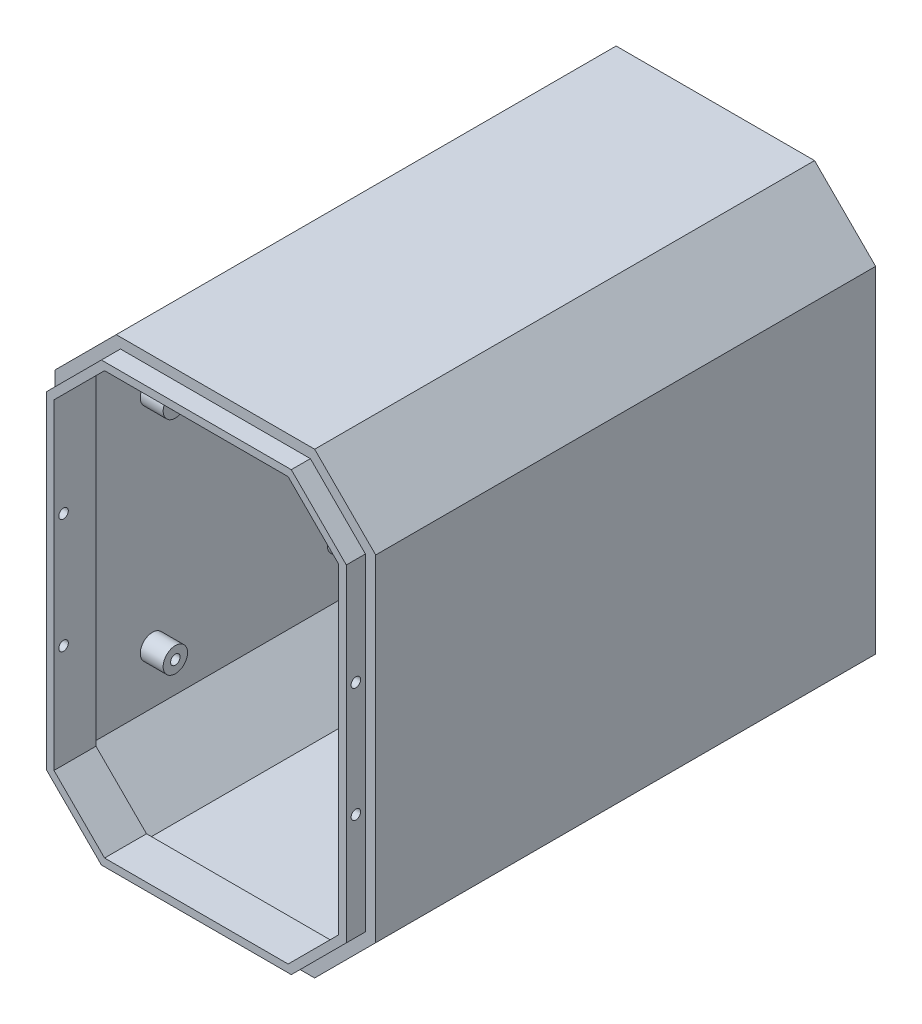
SolidWorks part; units mm, degrees
ref_plane "Front Plane" through (0, 0, 0) normal (0, 0, 1) x (1, 0, 0)
ref_plane "Top Plane" through (0, 0, 0) normal (0, 1, 0) x (1, 0, 0)
ref_plane "Right Plane" through (0, 0, 0) normal (1, 0, 0) x (0, 0, -1)
ref_plane "PZ_p37_000" through (0, 0, 37) normal (0, 0, 1) x (1, 0, 0)
sketch "S_prism1" plane through (0, 0, 37) normal (0, 0, 1) x (1, 0, 0)
  line L0 (42, -44) -> (42, 44)
  line L1 (42, 44) -> (26, 60)
  line L2 (26, 60) -> (-26, 60)
  line L3 (-26, 60) -> (-42, 44)
  line L4 (-42, 44) -> (-42, -44)
  line L5 (-42, -44) -> (-26, -60)
  line L6 (-26, -60) -> (26, -60)
  line L7 (26, -60) -> (42, -44)
extrude "Boss_1" add sketch "S_prism1" along normal blind 131
ref_plane "PZ_p71_125" through (0, 0, 71.125) normal (0, 0, 1) x (1, 0, 0)
sketch "S_pcut2" plane through (0, 0, 71.125) normal (0, 0, 1) x (1, 0, 0)
  line L0 (39.5, -42.9645) -> (39.5, 42.9645)
  line L1 (39.5, 42.9645) -> (24.9645, 57.5)
  line L2 (24.9645, 57.5) -> (-24.9645, 57.5)
  line L3 (-24.9645, 57.5) -> (-39.5, 42.9645)
  line L4 (-39.5, 42.9645) -> (-39.5, -42.9645)
  line L5 (-39.5, -42.9645) -> (-24.9645, -57.5)
  line L6 (-24.9645, -57.5) -> (24.9645, -57.5)
  line L7 (24.9645, -57.5) -> (39.5, -42.9645)
extrude "Cut_2" cut sketch "S_pcut2" along normal blind 96.975
ref_plane "PZ_p36_900" through (0, 0, 36.9) normal (0, 0, 1) x (1, 0, 0)
sketch "S_pcut3" plane through (0, 0, 36.9) normal (0, 0, 1) x (1, 0, 0)
  line L0 (39.5, -42.9645) -> (39.5, 42.9645)
  line L1 (39.5, 42.9645) -> (24.9645, 57.5)
  line L2 (24.9645, 57.5) -> (-24.9645, 57.5)
  line L3 (-24.9645, 57.5) -> (-39.5, 42.9645)
  line L4 (-39.5, 42.9645) -> (-39.5, -42.9645)
  line L5 (-39.5, -42.9645) -> (-24.9645, -57.5)
  line L6 (-24.9645, -57.5) -> (24.9645, -57.5)
  line L7 (24.9645, -57.5) -> (39.5, -42.9645)
extrude "Cut_3" cut sketch "S_pcut3" along normal blind 31.725
ref_plane "PZ_p68_525" through (0, 0, 68.525) normal (0, 0, 1) x (1, 0, 0)
sketch "S_cut4" plane through (0, 0, 68.525) normal (0, 0, 1) x (1, 0, 0)
  line L0 (-34, -14) -> (-26, -14)
  line L1 (-26, -14) -> (-26, 14)
  line L2 (-26, 14) -> (-34, 14)
  line L3 (-34, 14) -> (-34, -14)
  dimension "P1" = 34
  dimension "P2" = 14
  dimension "P3" = 26
  dimension "P4" = 14
  dimension "P5" = 26
  dimension "P6" = 14
  dimension "P7" = 34
  dimension "P8" = 14
extrude "Pocket_4" cut sketch "S_cut4" along normal blind 2.7
ref_plane "PX_m42_100" through (-42.1, 0, 0) normal (1, 0, 0) x (0, 0, -1)
sketch "S_hole5" plane through (-42.1, 0, 0) normal (1, 0, 0) x (0, 0, -1)
  circle A0 centre (-88, 0) radius 6
  dimension "D1_S_hole5" = 12
  dimension "P2" = 88
extrude "Hole_5" cut sketch "S_hole5" along normal blind 2.7
sketch "S_hole6" plane through (0, 0, 68.525) normal (0, 0, 1) x (1, 0, 0)
  circle A0 centre (-20, -25) radius 1.6
  dimension "D1_S_hole6" = 3.2
  dimension "P2" = 20
  dimension "P3" = 25
extrude "Hole_6" cut sketch "S_hole6" along normal blind 2.7
sketch "S_hole7" plane through (0, 0, 68.525) normal (0, 0, 1) x (1, 0, 0)
  circle A0 centre (-20, 25) radius 1.6
  dimension "D1_S_hole7" = 3.2
  dimension "P2" = 20
  dimension "P3" = 25
extrude "Hole_7" cut sketch "S_hole7" along normal blind 2.7
sketch "S_hole8" plane through (0, 0, 68.525) normal (0, 0, 1) x (1, 0, 0)
  circle A0 centre (24, -25) radius 1.6
  dimension "D1_S_hole8" = 3.2
  dimension "P2" = 24
  dimension "P3" = 25
extrude "Hole_8" cut sketch "S_hole8" along normal blind 2.7
sketch "S_hole9" plane through (0, 0, 68.525) normal (0, 0, 1) x (1, 0, 0)
  circle A0 centre (24, 25) radius 1.6
  dimension "D1_S_hole9" = 3.2
  dimension "P2" = 24
  dimension "P3" = 25
extrude "Hole_9" cut sketch "S_hole9" along normal blind 2.7
ref_plane "PZ_p162_000" through (0, 0, 162) normal (0, 0, 1) x (1, 0, 0)
sketch "S_prism10" plane through (0, 0, 162) normal (0, 0, 1) x (1, 0, 0)
  line L0 (40, -43.1716) -> (40, 43.1716)
  line L1 (40, 43.1716) -> (25.1716, 58)
  line L2 (25.1716, 58) -> (-25.1716, 58)
  line L3 (-25.1716, 58) -> (-40, 43.1716)
  line L4 (-40, 43.1716) -> (-40, -43.1716)
  line L5 (-40, -43.1716) -> (-25.1716, -58)
  line L6 (-25.1716, -58) -> (25.1716, -58)
  line L7 (25.1716, -58) -> (40, -43.1716)
extrude "Boss_10" add sketch "S_prism10" along normal blind 6
ref_plane "PZ_p167_900" through (0, 0, 167.9) normal (0, 0, 1) x (1, 0, 0)
sketch "S_prism11" plane through (0, 0, 167.9) normal (0, 0, 1) x (1, 0, 0)
  line L0 (39.3, -42.8816) -> (39.3, 42.8816)
  line L1 (39.3, 42.8816) -> (24.8816, 57.3)
  line L2 (24.8816, 57.3) -> (-24.8816, 57.3)
  line L3 (-24.8816, 57.3) -> (-39.3, 42.8816)
  line L4 (-39.3, 42.8816) -> (-39.3, -42.8816)
  line L5 (-39.3, -42.8816) -> (-24.8816, -57.3)
  line L6 (-24.8816, -57.3) -> (24.8816, -57.3)
  line L7 (24.8816, -57.3) -> (39.3, -42.8816)
extrude "Boss_11" add sketch "S_prism11" along normal blind 5.1
ref_plane "PX_m40_000" through (-40, 0, 0) normal (1, 0, 0) x (0, 0, -1)
sketch "S_cyl12" plane through (-40, 0, 0) normal (1, 0, 0) x (0, 0, -1)
  circle A0 centre (-96, -29) radius 3.2
  dimension "D1_S_cyl12" = 6.4
  dimension "P2" = 96
  dimension "P3" = 29
extrude "Boss_12" add sketch "S_cyl12" along normal blind 6.5
sketch "S_cyl13" plane through (-40, 0, 0) normal (1, 0, 0) x (0, 0, -1)
  circle A0 centre (-145, -29) radius 3.2
  dimension "D1_S_cyl13" = 6.4
  dimension "P2" = 145
  dimension "P3" = 29
extrude "Boss_13" add sketch "S_cyl13" along normal blind 6.5
sketch "S_cyl14" plane through (-40, 0, 0) normal (1, 0, 0) x (0, 0, -1)
  circle A0 centre (-96, 29) radius 3.2
  dimension "D1_S_cyl14" = 6.4
  dimension "P2" = 96
  dimension "P3" = 29
extrude "Boss_14" add sketch "S_cyl14" along normal blind 6.5
sketch "S_cyl15" plane through (-40, 0, 0) normal (1, 0, 0) x (0, 0, -1)
  circle A0 centre (-145, 29) radius 3.2
  dimension "D1_S_cyl15" = 6.4
  dimension "P2" = 145
  dimension "P3" = 29
extrude "Boss_15" add sketch "S_cyl15" along normal blind 6.5
ref_plane "PZ_p161_900" through (0, 0, 161.9) normal (0, 0, 1) x (1, 0, 0)
sketch "S_pcut16" plane through (0, 0, 161.9) normal (0, 0, 1) x (1, 0, 0)
  line L0 (37.3, -42.0532) -> (37.3, 42.0532)
  line L1 (37.3, 42.0532) -> (24.0532, 55.3)
  line L2 (24.0532, 55.3) -> (-24.0532, 55.3)
  line L3 (-24.0532, 55.3) -> (-37.3, 42.0532)
  line L4 (-37.3, 42.0532) -> (-37.3, -42.0532)
  line L5 (-37.3, -42.0532) -> (-24.0532, -55.3)
  line L6 (-24.0532, -55.3) -> (24.0532, -55.3)
  line L7 (24.0532, -55.3) -> (37.3, -42.0532)
extrude "Cut_16" cut sketch "S_pcut16" along normal blind 11.2
ref_plane "PX_p37_100" through (37.1, 0, 0) normal (1, 0, 0) x (0, 0, -1)
sketch "S_hole17" plane through (37.1, 0, 0) normal (1, 0, 0) x (0, 0, -1)
  circle A0 centre (-170.5, -15) radius 1.25
  dimension "D1_S_hole17" = 2.5
  dimension "P2" = 170.5
  dimension "P3" = 15
extrude "Hole_17" cut sketch "S_hole17" along normal blind 2.7
sketch "S_hole18" plane through (37.1, 0, 0) normal (1, 0, 0) x (0, 0, -1)
  circle A0 centre (-170.5, 15) radius 1.25
  dimension "D1_S_hole18" = 2.5
  dimension "P2" = 170.5
  dimension "P3" = 15
extrude "Hole_18" cut sketch "S_hole18" along normal blind 2.7
ref_plane "PX_m39_800" through (-39.8, 0, 0) normal (1, 0, 0) x (0, 0, -1)
sketch "S_hole19" plane through (-39.8, 0, 0) normal (1, 0, 0) x (0, 0, -1)
  circle A0 centre (-170.5, -15) radius 1.25
  dimension "D1_S_hole19" = 2.5
  dimension "P2" = 170.5
  dimension "P3" = 15
extrude "Hole_19" cut sketch "S_hole19" along normal blind 2.7
sketch "S_hole20" plane through (-39.8, 0, 0) normal (1, 0, 0) x (0, 0, -1)
  circle A0 centre (-170.5, 15) radius 1.25
  dimension "D1_S_hole20" = 2.5
  dimension "P2" = 170.5
  dimension "P3" = 15
extrude "Hole_20" cut sketch "S_hole20" along normal blind 2.7
ref_plane "PX_m39_500" through (-39.5, 0, 0) normal (1, 0, 0) x (0, 0, -1)
sketch "S_hole21" plane through (-39.5, 0, 0) normal (1, 0, 0) x (0, 0, -1)
  circle A0 centre (-96, -29) radius 1.25
  dimension "D1_S_hole21" = 2.5
  dimension "P2" = 96
  dimension "P3" = 29
extrude "Hole_21" cut sketch "S_hole21" along normal blind 6.1
sketch "S_hole22" plane through (-39.5, 0, 0) normal (1, 0, 0) x (0, 0, -1)
  circle A0 centre (-145, -29) radius 1.25
  dimension "D1_S_hole22" = 2.5
  dimension "P2" = 145
  dimension "P3" = 29
extrude "Hole_22" cut sketch "S_hole22" along normal blind 6.1
sketch "S_hole23" plane through (-39.5, 0, 0) normal (1, 0, 0) x (0, 0, -1)
  circle A0 centre (-96, 29) radius 1.25
  dimension "D1_S_hole23" = 2.5
  dimension "P2" = 96
  dimension "P3" = 29
extrude "Hole_23" cut sketch "S_hole23" along normal blind 6.1
sketch "S_hole24" plane through (-39.5, 0, 0) normal (1, 0, 0) x (0, 0, -1)
  circle A0 centre (-145, 29) radius 1.25
  dimension "D1_S_hole24" = 2.5
  dimension "P2" = 145
  dimension "P3" = 29
extrude "Hole_24" cut sketch "S_hole24" along normal blind 6.1
equation "\"plate_t\" = 3"
equation "\"clearance\" = 0.4"
